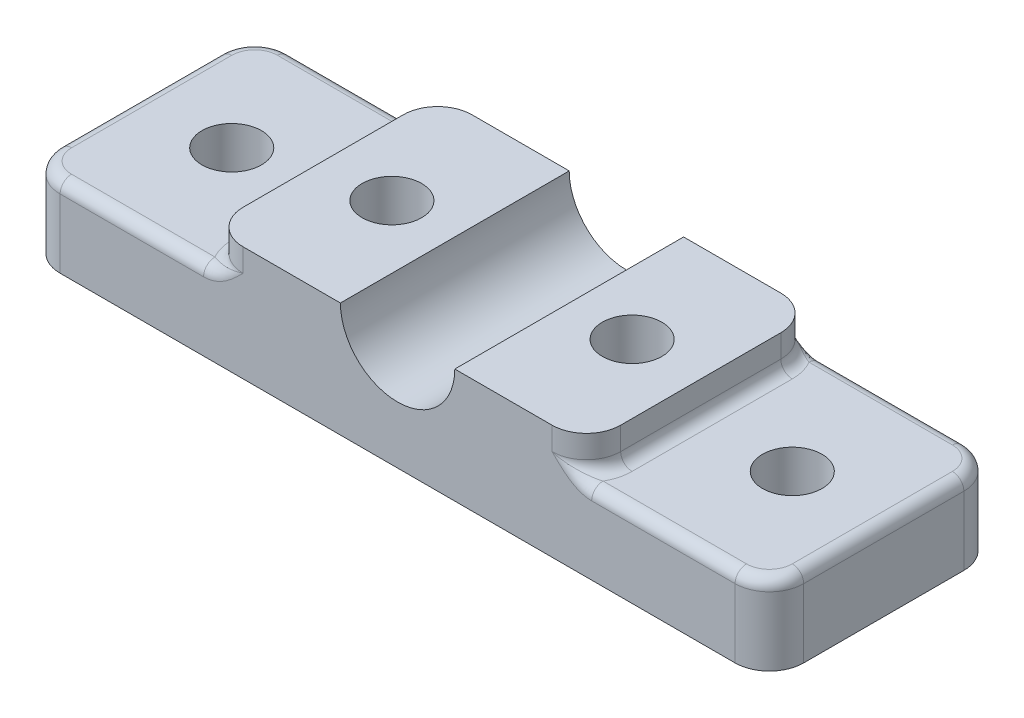
SolidWorks part; units mm, degrees
material "ABS"
ref_plane "Front Plane" through (0, 0, 0) normal (0, 0, 1) x (1, 0, 0)
ref_plane "Top Plane" through (0, 0, 0) normal (0, 1, 0) x (1, 0, 0)
ref_plane "Right Plane" through (0, 0, 0) normal (1, 0, 0) x (0, 0, -1)
sketch "Sketch1" plane through (0, 0, 0) normal (0, 1, 0) x (1, 0, 0)
  line L0 (-50.7915, 0) -> (50.7915, 0) construction
  line L1 (0, 10) -> (0, -10) construction
  line L2 (-29.5, -10) -> (29.5, -10)
  line L3 (-32.5, -7) -> (-32.5, 7)
  line L4 (-29.5, 10) -> (29.5, 10)
  line L5 (32.5, -7) -> (32.5, 7)
  line L6 (-32.5, -10) -> (32.5, 10) construction
  line L7 (-32.5, 10) -> (32.5, -10) construction
  line L8 (-16.5, -10) -> (16.5, -10) construction
  line L9 (-16.5, -10) -> (-16.5, 10) construction
  line L10 (-16.5, 10) -> (16.5, 10) construction
  line L11 (16.5, -10) -> (16.5, 10) construction
  line L12 (-16.5, -10) -> (16.5, 10) construction
  line L13 (-16.5, 10) -> (16.5, -10) construction
  arc A0 (-32.5, -7) -> (-29.5, -10) centre (-29.5, -7) ccw
  arc A1 (29.5, -10) -> (32.5, -7) centre (29.5, -7) ccw
  arc A2 (32.5, 7) -> (29.5, 10) centre (29.5, 7) ccw
  arc A3 (-29.5, 10) -> (-32.5, 7) centre (-29.5, 7) ccw
  circle A4 centre (-10.5, 0) radius 2.6
  circle A5 centre (-24.5, 0) radius 2.6
  circle A6 centre (24.5, 0) radius 2.6
  circle A7 centre (10.5, 0) radius 2.6
  point P3 (0, 0)
  point P4 (0, 0)
  point P25 (0, 0)
  dimension "D3" = 3
  dimension "D4" = 5.2
  dimension "D7" = 14
  dimension "D1" = 65
  dimension "D2" = 20
  dimension "D5" = 33
  dimension "D6" = 10.5
extrude "Boss-Extrude1" add sketch "Sketch1" along normal blind 7
sketch "Sketch2" plane through (0, 7, 0) normal (0, 1, 0) x (1, 0, 0)
  line L0 (29.5, 10) -> (-29.5, 10) construction
  line L1 (-13.5, -10) -> (13.5, -10)
  line L2 (-16.5, -7) -> (-16.5, 7)
  line L3 (-13.5, 10) -> (13.5, 10)
  line L4 (16.5, -7) -> (16.5, 7)
  line L5 (-16.5, -10) -> (16.5, 10) construction
  line L6 (-16.5, 10) -> (16.5, -10) construction
  arc A0 (13.5, 10) -> (16.5, 7) centre (13.5, 7) cw
  arc A1 (16.5, -7) -> (13.5, -10) centre (13.5, -7) cw
  arc A2 (-13.5, -10) -> (-16.5, -7) centre (-13.5, -7) cw
  arc A3 (-16.5, 7) -> (-13.5, 10) centre (-13.5, 7) cw
  circle A4 centre (-10.5, 0) radius 2.6 construction
  circle A5 centre (10.5, 0) radius 2.6 construction
  circle A6 centre (-10.5, 0) radius 2.6
  circle A7 centre (10.5, 0) radius 2.6
  point P0 (0, 0)
  dimension "D2" = 3
  dimension "D1" = 33
extrude "Boss-Extrude2" add sketch "Sketch2" along normal blind 3
sketch "Sketch3" plane through (0, 0, 10) normal (0, 0, 1) x (1, 0, 0)
  line L0 (0, 0) -> (0, 16.2371) construction
  line L1 (-29.5, 0) -> (29.5, 0) construction
  circle A0 centre (0, 10) radius 5
  dimension "D1" = 10
  dimension "D2" = 10
extrude "Cut-Extrude1" cut sketch "Sketch3" against normal up to surface (20 mm away) up to face at (2, 6.375, -10)
sketch "Sketch4" plane through (0, 0, 0) normal (0, -1, 0) x (1, 0, 0)
  line L0 (-32.5, -7) -> (-32.5, 7) construction
  line L1 (-10.5, 4.6188) -> (-14.5, 2.3094)
  line L2 (-14.5, 2.3094) -> (-14.5, -2.3094)
  line L3 (-14.5, -2.3094) -> (-10.5, -4.6188)
  line L4 (-10.5, -4.6188) -> (-6.5, -2.3094)
  line L5 (-6.5, -2.3094) -> (-6.5, 2.3094)
  line L6 (-6.5, 2.3094) -> (-10.5, 4.6188)
  line L7 (14.5, 2.3094) -> (10.5, 4.6188)
  line L8 (10.5, 4.6188) -> (6.5, 2.3094)
  line L9 (6.5, 2.3094) -> (6.5, -2.3094)
  line L10 (6.5, -2.3094) -> (10.5, -4.6188)
  line L11 (10.5, -4.6188) -> (14.5, -2.3094)
  line L12 (14.5, -2.3094) -> (14.5, 2.3094)
  line L13 (32.5, 7) -> (32.5, -7) construction
  circle A0 centre (-10.5, 0) radius 4 construction
  circle A1 centre (10.5, 0) radius 4 construction
  dimension "D1" = 8
extrude "Cut-Extrude2" cut sketch "Sketch4" against normal blind 5
fillet "Fillet1" radius 1 16 edges at (-16.5, 7, 0) (16.5, 7, 0) (31.6213, 7, -9.1213) (32.5, 7, 0) (-31.6213, 7, -9.1213) (-32.5, 7, 0) (31.6213, 7, 9.1213) (-31.6213, 7, 9.1213)
sketch "Sketch5" plane through (0, 5, 0) normal (0, -1, 0) x (1, 0, 0)
  circle A0 centre (10.5, 0) radius 2.6 construction
  circle A1 centre (-10.5, 0) radius 2.6 construction
  circle A2 centre (10.5, 0) radius 2.6
  circle A3 centre (-10.5, 0) radius 2.6
extrude "Boss-Extrude3" [suppressed] add sketch "Sketch5" against normal blind 0.2
